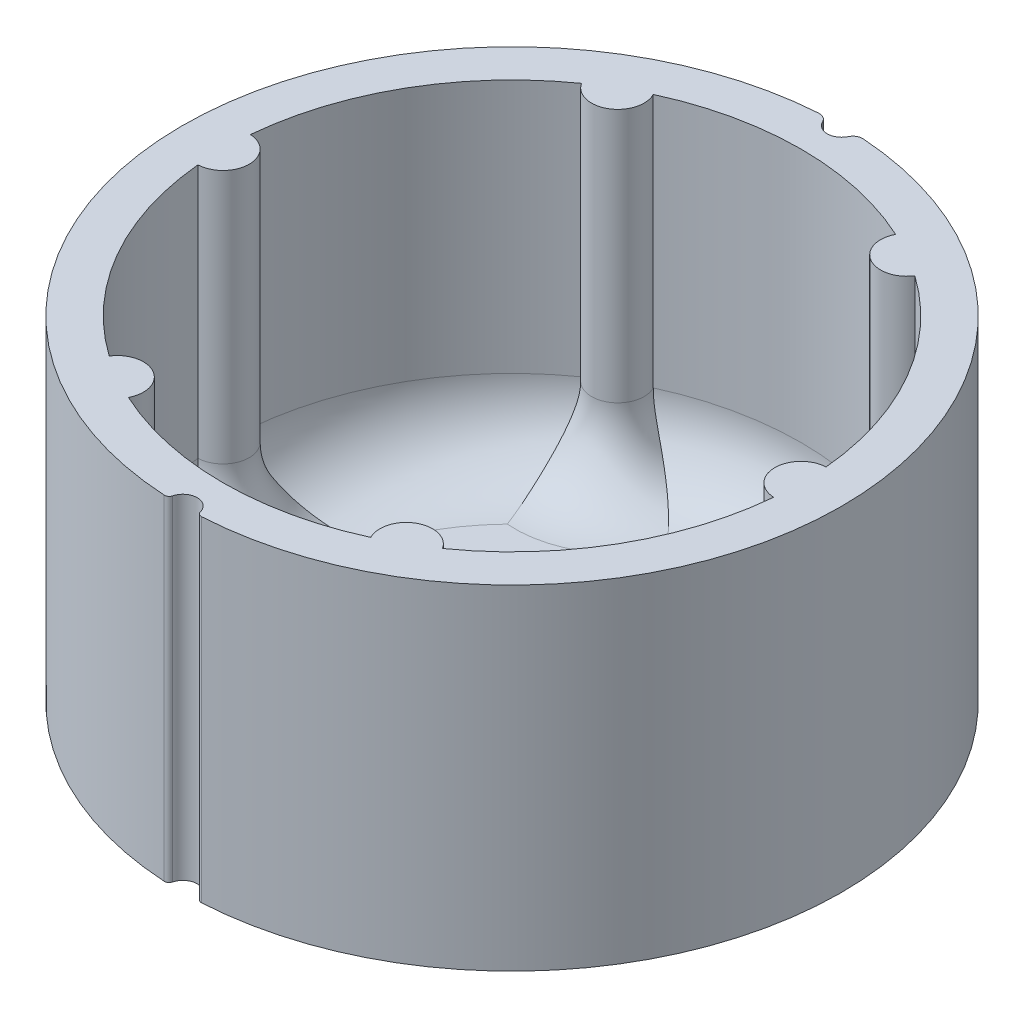
SolidWorks part; units mm, degrees
ref_plane "Front Plane" through (0, 0, 0) normal (0, 0, 1) x (1, 0, 0)
ref_plane "Top Plane" through (0, 0, 0) normal (0, 1, 0) x (1, 0, 0)
ref_plane "Right Plane" through (0, 0, 0) normal (1, 0, 0) x (0, 0, -1)
sketch "Sketch1" plane through (0, 0, 0) normal (0, 1, 0) x (1, 0, 0)
  line L3 (0, 0.002) -> (0, 3.7877) construction
  line L4 (0, 3.7877) -> (2.417, 3.7877)
  line L5 (0, 3.7877) -> (-2.417, 3.7877)
  arc A0 (1.9642, -34.442) -> (34.1982, 4.5552) centre (0, 0.002) ccw
  arc A2 (-2.417, 3.7877) -> (2.417, 3.7877) centre (0, 0.002) ccw
  circle A3 centre (0, 0.002) radius 34.5 construction
  arc A7 (-1.3541, 33.8562) -> (1.3541, 33.8562) centre (0, 34.5015) ccw
  arc A8 (34.1982, 4.5552) -> (2.3241, 34.4236) centre (0, 0.002) ccw
  arc A9 (-2.3241, 34.4236) -> (-34.1982, 4.5552) centre (0, 0.002) ccw
  arc A10 (-34.1982, 4.5552) -> (-1.9642, -34.442) centre (0, 0.002) ccw
  arc A11 (1.3541, 33.8562) -> (2.3241, 34.4236) centre (2.2568, 33.4259) cw
  arc A12 (-1.3541, 33.8562) -> (-2.3241, 34.4236) centre (-2.2568, 33.4259) ccw
  arc A13 (1.4518, -34.0686) -> (-1.4518, -34.0686) centre (0, -34.4457) ccw
  arc A14 (1.4518, -34.0686) -> (1.9642, -34.442) centre (1.9358, -33.9428) ccw
  arc A15 (-1.4518, -34.0686) -> (-1.9642, -34.442) centre (-1.9358, -33.9428) cw
  point P15 (1.4997, 34.4694)
  dimension "D2" = 4.834
  dimension "D3" = 4.4915
  dimension "D4" = 34.5
  dimension "D5" = 1
  dimension "D6" = 1.5
  dimension "D7" = 0.5
  dimension "D11" = 1.4997
sketch "Sketch2" plane through (0, 0, 0) normal (0, 1, 0) x (1, 0, 0)
  arc A16 (-17.4416, 24.7154) -> (-30.125, 2.7472) centre (0, 0) ccw
  circle A23 centre (0, 0) radius 27.5 construction
  arc A24 (30.125, 2.7472) -> (30.125, -2.7472) centre (30.25, 0) ccw
  arc A25 (17.4416, -24.7154) -> (12.6834, -27.4626) centre (15.125, -26.1973) ccw
  arc A26 (-12.6834, -27.4626) -> (-17.4416, -24.7154) centre (-15.125, -26.1973) ccw
  arc A27 (-30.125, -2.7472) -> (-30.125, 2.7472) centre (-30.25, 0) ccw
  arc A28 (-17.4416, 24.7154) -> (-12.6834, 27.4626) centre (-15.125, 26.1973) ccw
  arc A29 (12.6834, 27.4626) -> (17.4416, 24.7154) centre (15.125, 26.1973) ccw
  arc A30 (-30.125, -2.7472) -> (-17.4416, -24.7154) centre (0, 0) ccw
  arc A31 (-12.6834, -27.4626) -> (12.6834, -27.4626) centre (0, 0) ccw
  arc A32 (17.4416, -24.7154) -> (30.125, -2.7472) centre (0, 0) ccw
  arc A33 (30.125, 2.7472) -> (17.4416, 24.7154) centre (0, 0) ccw
  arc A34 (12.6834, 27.4626) -> (-12.6834, 27.4626) centre (0, 0) ccw
  dimension "D1" = 60.5
  dimension "D2" = 55
  dimension "D3" = 6
extrude "Boss-Extrude1" add sketch "Sketch1" along normal blind 35 contours A10 A0 A8 A7 A9 A2 L5 L4 region at (2.2155, 0, 33.5591)
extrude "Cut-Extrude2" cut sketch "Sketch2" along normal through all
extrude "Boss-Extrude2" add sketch "Sketch2<2>" along normal blind 0.4
sketch "Sketch2<2>" plane through (0, 0, 0) normal (0, 1, 0) x (1, 0, 0) same geometry as "Sketch2"
fillet "Fillet1" radius 8 12 edges at (13.75, 0.4, 23.8157) (0, 0.4, 30.25) (-13.75, 0.4, 23.8157) (-26.1973, 0.4, 15.125) (-27.5, 0.4, 0) (-26.1973, 0.4, -15.125) (-13.75, 0.4, -23.8157) (0, 0.4, -30.25) (13.75, 0.4, -23.8157) (26.1973, 0.4, -15.125) (27.5, 0.4, 0) (26.1973, 0.4, 15.125)
equation "\"2.5.00mm\"=3"
